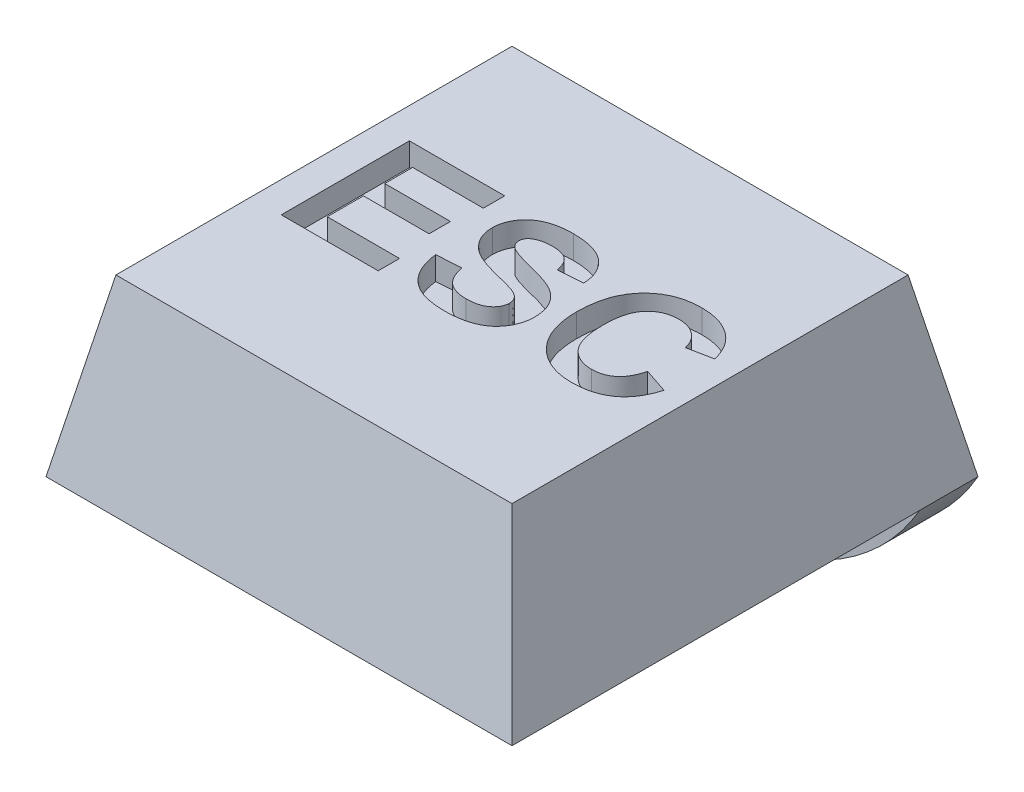
SolidWorks part; units mm, degrees
ref_plane "Front Plane" through (0, 0, 0) normal (0, 0, 1) x (1, 0, 0)
ref_plane "Top Plane" through (0, 0, 0) normal (0, 1, 0) x (1, 0, 0)
ref_plane "Right Plane" through (0, 0, 0) normal (1, 0, 0) x (0, 0, -1)
sketch "Sketch1" plane through (0, 0, 0) normal (0, 1, 0) x (1, 0, 0)
  line L1 (0, 0) -> (8, 0)
  line L2 (0, 0) -> (0, 8)
  line L3 (0, 8) -> (8, 8)
  line L4 (8, 0) -> (8, 8)
  dimension "D1" = 8
  dimension "D2" = 8
extrude "Boss-Extrude1" add sketch "Sketch1" along normal blind 3
sketch "Sketch2" plane through (0, 0, 0) normal (0, 0, 1) x (1, 0, 0)
  line L0 (0, 0) -> (0.6, 3)
  line L1 (0, 3) -> (8, 3) construction
  line L2 (0.6, 3) -> (0, 3)
  line L3 (0, 3) -> (0, 0)
  line L4 (8, 0) -> (7.4, 3)
  line L5 (7.4, 3) -> (8, 3)
  line L6 (8, 3) -> (8, 0)
  dimension "D1" = 0.6
  dimension "D2" = 0.6
extrude "Cut-Extrude1" cut sketch "Sketch2" against normal through all both and the other way through all
sketch "Sketch3" plane through (0, 0, 0) normal (1, 0, 0) x (0, 0, -1)
  line L0 (0, 0) -> (0.6, 3)
  line L1 (8, 3) -> (0, 3) construction
  line L2 (0.6, 3) -> (0, 3)
  line L3 (0, 3) -> (0, 0)
  line L4 (8, 3) -> (7.4, 3)
  line L5 (7.4, 3) -> (8, 0)
  line L6 (8, 3) -> (8, 0)
  dimension "D1" = 0.6
  dimension "D2" = 0.6
extrude "Cut-Extrude2" cut sketch "Sketch3" along normal blind 11
sketch "Sketch4" plane through (0, 0, 0) normal (0, -1, 0) x (1, 0, 0)
  line L0 (8, 0) -> (8, -8) construction
  line L3 (0, 0) -> (8, 0) construction
  circle A0 centre (4, -3.75) radius 1.8
  dimension "D1" = 3.6
  dimension "D2" = 4
  dimension "D3" = 3.75
extrude "Cut-Extrude3" cut sketch "Sketch4" against normal blind 0.8
sketch "Sketch5" plane through (0, 0, 0) normal (0, -1, 0) x (1, 0, 0)
  line L0 (8, 0) -> (8, -8) construction
  line L1 (0, -8) -> (8, -8)
  line L2 (0, -8) -> (0, -7)
  line L3 (0, -7) -> (8, -7)
  line L4 (8, -8) -> (8, -7)
  dimension "D1" = 1
extrude "Boss-Extrude2" add sketch "Sketch5" along normal blind 2
fillet "Fillet1" radius 4 2 edges at (8, -2, -7.5) (0, -2, -7.5)
sketch "Sketch6" plane through (0, 3, 0) normal (0, 1, 0) x (1, 0, 0)
  text T0 "ESC" font "Arial" height 2.2
extrude "Cut-Extrude4" cut sketch "Sketch6" against normal blind 0.4
